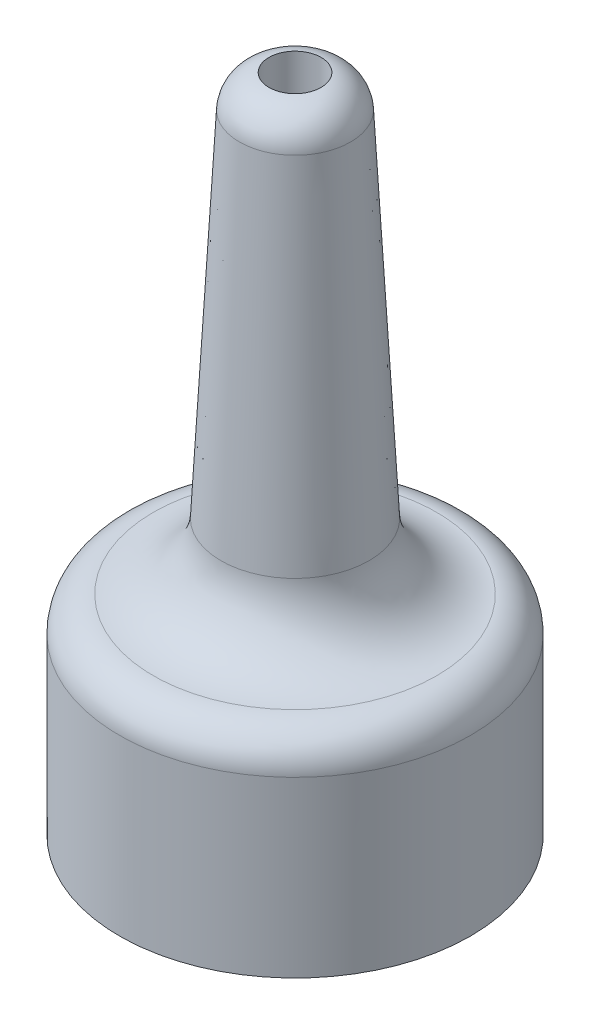
SolidWorks part; units mm, degrees
ref_plane "Front Plane" through (0, 0, 0) normal (0, 0, 1) x (1, 0, 0)
ref_plane "Top Plane" through (0, 0, 0) normal (0, 1, 0) x (1, 0, 0)
ref_plane "Right Plane" through (0, 0, 0) normal (1, 0, 0) x (0, 0, -1)
sketch "Sketch2" plane through (0, 0, 0) normal (0, 0, 1) x (1, 0, 0)
  line L0 (-1.55, 12.9822) -> (-2.2304, 0)
  line L1 (-2.2304, 0) -> (-5.05, 0)
  line L2 (-5.05, 0) -> (-5.05, -6)
  line L3 (-5.05, -6) -> (-3.95, -6)
  line L4 (-3.95, -6) -> (-3.95, -1)
  line L5 (-3.95, -1) -> (-0.75, -1)
  line L6 (-0.75, -1) -> (-0.75, 13)
  line L7 (-0.75, 13) -> (-1.55, 12.9822)
  line L8 (0, -1000) -> (0, 49000) construction
  dimension "D1" = 0.75
  dimension "D2" = 93
  dimension "D3" = 13
  dimension "D4" = 1
  dimension "D5" = 3.95
  dimension "D6" = 5.05
  dimension "D7" = 6
  dimension "D8" = 0.8
  dimension "D9" = 14
revolve "Revolve1" add sketch "Sketch2" angle 360 about L8
fillet "Fillet2" radius 2 1 edges at (2.2304, 0, 0) type face fillet first side face at (2.2304, 0, 0) second side face at (5.05, 0, 0)
fillet "Fillet3" radius 1 1 edges at (5.05, 0, 0)
fillet "Fillet4" radius 1 1 edges at (1.55, 12.9822, 0)
